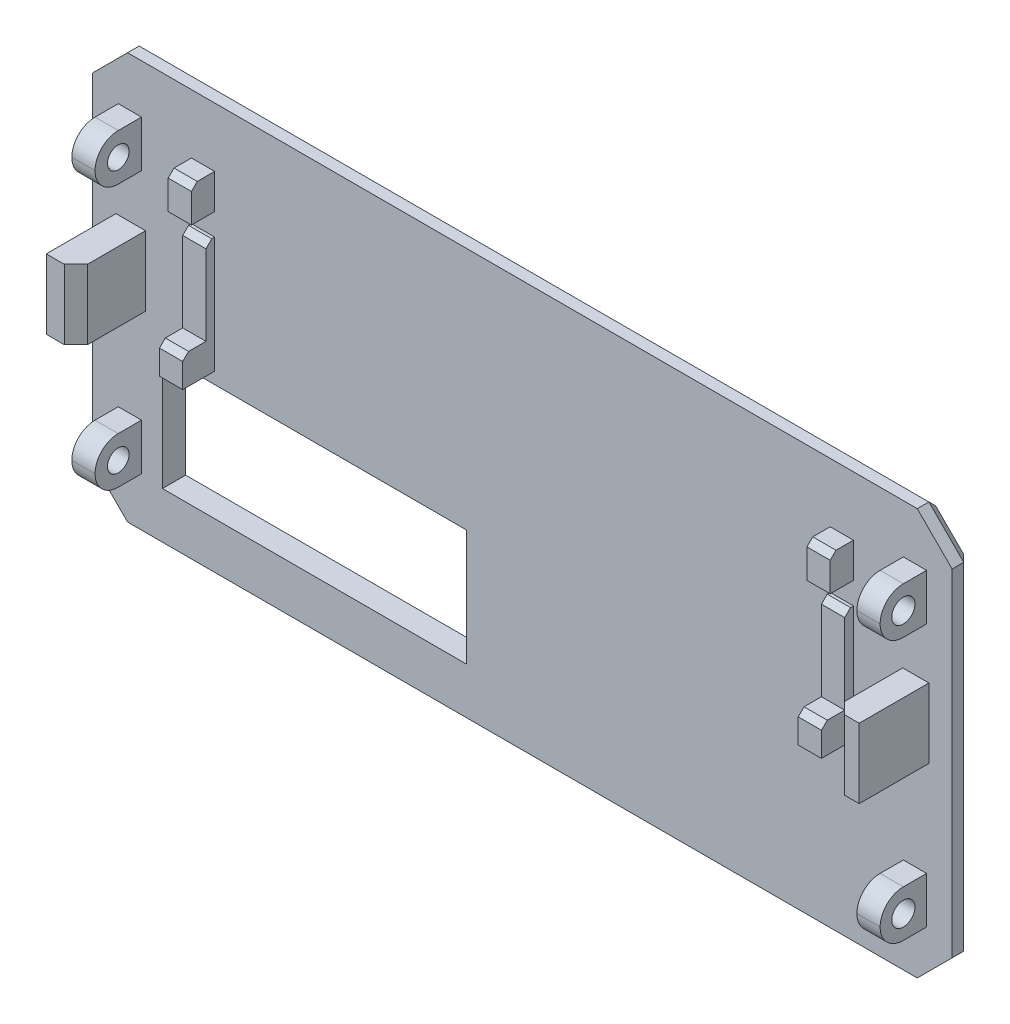
SolidWorks part; units mm, degrees
ref_plane "前视基准面" through (0, 0, 0) normal (0, 0, 1) x (1, 0, 0)
ref_plane "上视基准面" through (0, 0, 0) normal (0, 1, 0) x (1, 0, 0)
ref_plane "右视基准面" through (0, 0, 0) normal (1, 0, 0) x (0, 0, -1)
other "Configuration Table"
sketch "草图1" plane through (0, 0, 0) normal (0, 0, 1) x (1, 0, 0)
  line L0 (-39.7638, 14.7992) -> (-36.7638, 17.7992)
  line L5 (-36.7638, 17.7992) -> (31.2362, 17.7992)
  line L6 (-39.7638, 14.7992) -> (-39.7638, -14.2008)
  line L7 (-36.7638, -17.2008) -> (31.2362, -17.2008)
  line L8 (34.2362, 14.7992) -> (34.2362, -14.2008)
  line L9 (-39.7638, -14.2008) -> (-36.7638, -17.2008)
  line L10 (31.2362, -17.2008) -> (34.2362, -14.2008)
  line L11 (31.2362, 17.7992) -> (34.2362, 14.7992)
  point P0 (-39.7638, 17.7992)
  point P1 (34.2362, -17.2008)
  point P2 (-39.7638, -17.2008)
  point P3 (34.2362, 17.7992)
  dimension "D1" = 74
  dimension "D2" = 35
extrude "凸台-拉伸1" add sketch "草图1" along normal blind 2
chamfer "倒角1" distance 1 angle 45 8 edges at (-38.2638, 16.2992, 0) (-2.7638, -17.2008, 0) (-39.7638, 0.2992, 0) (-38.2638, -15.7008, 0) (32.7362, -15.7008, 0) (34.2362, 0.2992, 0) (32.7362, 16.2992, 0) (-2.7638, 17.7992, 0)
sketch "草图3" plane through (0, 0, 2) normal (0, 0, 1) x (1, 0, 0)
  line L0 (-36.7638, 17.7992) -> (31.2362, 17.7992) construction
  line L1 (-37.5638, 13.5992) -> (-35.5638, 13.5992)
  line L2 (-37.5638, 13.5992) -> (-37.5638, 9.5992)
  line L3 (-37.5638, 9.5992) -> (-35.5638, 9.5992)
  line L4 (-35.5638, 13.5992) -> (-35.5638, 9.5992)
  line L5 (-37.5638, -13.0008) -> (-35.5638, -13.0008)
  line L6 (-37.5638, -13.0008) -> (-37.5638, -9.0008)
  line L7 (-37.5638, -9.0008) -> (-35.5638, -9.0008)
  line L8 (-35.5638, -13.0008) -> (-35.5638, -9.0008)
  line L9 (32.0362, 13.5992) -> (30.0362, 13.5992)
  line L10 (32.0362, 13.5992) -> (32.0362, 9.5992)
  line L11 (32.0362, 9.5992) -> (30.0362, 9.5992)
  line L12 (30.0362, 13.5992) -> (30.0362, 9.5992)
  line L13 (32.0362, -13.0008) -> (30.0362, -13.0008)
  line L14 (32.0362, -13.0008) -> (32.0362, -9.0008)
  line L15 (32.0362, -9.0008) -> (30.0362, -9.0008)
  line L16 (30.0362, -13.0008) -> (30.0362, -9.0008)
  line L17 (-39.7638, -14.2008) -> (-39.7638, 14.7992) construction
  line L18 (34.2362, 14.7992) -> (34.2362, -14.2008) construction
  line L19 (31.2362, -17.2008) -> (-36.7638, -17.2008) construction
  point P20 (0, 0)
  point P21 (0, 0)
  point P22 (0, 0)
  point P23 (0, 0)
  point P24 (0, 0)
  point P35 (0, 0)
  point P36 (0, 0)
  point P37 (0, 0)
  point P38 (0, 0)
  dimension "D1" = 2
  dimension "D2" = 4
  dimension "D3" = 4.2
  dimension "D4" = 2.2
  dimension "D5" = 2.2
  dimension "D6" = 4.2
extrude "凸台-拉伸2" add sketch "草图3" along normal blind 4
fillet "圆角1" radius 2 8 edges at (31.0362, 13.5992, 6) (31.0362, 9.5992, 6) (31.0362, -9.0008, 6) (31.0362, -13.0008, 6) (-36.5638, -13.0008, 6) (-36.5638, -9.0008, 6) (-36.5638, 13.5992, 6) (-36.5638, 9.5992, 6)
sketch "草图4" plane through (32.0362, 0, 0) normal (1, 0, 0) x (0, 0, -1)
  circle A0 centre (-4, 11.5992) radius 1
  circle A1 centre (-4, -11.0008) radius 1
  dimension "D1" = 2
extrude "切除-拉伸1" cut sketch "草图4" against normal up to next (2 mm away) draft 2
sketch "草图5" plane through (-37.5638, 0, 0) normal (-1, 0, 0) x (0, 0, 1)
  circle A0 centre (4, 11.5992) radius 1
  circle A1 centre (4, -11.0008) radius 1
  dimension "D1" = 2
extrude "切除-拉伸2" cut sketch "草图5" against normal up to next (2 mm away) draft 2
sketch "草图6" plane through (0, 0, 2) normal (0, 0, 1) x (1, 0, 0)
  line L0 (31.2362, 17.7992) -> (-36.7638, 17.7992) construction
  line L1 (-31.2638, 7.7992) -> (-29.2638, 7.7992)
  line L2 (-31.2638, 7.7992) -> (-31.2638, -2.2008)
  line L3 (-31.2638, -2.2008) -> (-29.2638, -2.2008)
  line L4 (-29.2638, 7.7992) -> (-29.2638, -2.2008)
  line L5 (23.7362, 7.7992) -> (25.7362, 7.7992)
  line L6 (23.7362, 7.7992) -> (23.7362, -2.2008)
  line L7 (23.7362, -2.2008) -> (25.7362, -2.2008)
  line L8 (25.7362, 7.7992) -> (25.7362, -2.2008)
  line L9 (-39.7638, 14.7992) -> (-39.7638, -14.2008) construction
  line L10 (34.2362, -14.2008) -> (34.2362, 14.7992) construction
  dimension "D1" = 10
  dimension "D2" = 10
  dimension "D3" = 8.5
  dimension "D4" = 8.5
  dimension "D5" = 10
  dimension "D6" = 2
extrude "凸台-拉伸3" add sketch "草图6" along normal blind 0.75
sketch "草图7" plane through (0, 0, 2.75) normal (0, 0, 1) x (1, 0, 0)
  line L0 (-29.2638, -2.2008) -> (-29.2638, 7.7992) construction
  line L1 (-31.2638, -2.2008) -> (-29.2638, -2.2008)
  line L2 (-31.2638, -2.2008) -> (-31.2638, 0.3992)
  line L3 (-31.2638, 0.3992) -> (-29.2638, 0.3992)
  line L4 (-29.2638, -2.2008) -> (-29.2638, 0.3992)
  line L5 (25.7362, -2.2008) -> (25.7362, 7.7992) construction
  line L6 (23.7362, -2.2008) -> (25.7362, -2.2008)
  line L7 (23.7362, -2.2008) -> (23.7362, 0.3992)
  line L8 (23.7362, 0.3992) -> (25.7362, 0.3992)
  line L9 (25.7362, -2.2008) -> (25.7362, 0.3992)
  dimension "D1" = 2.6
extrude "凸台-拉伸4" add sketch "草图7" along normal blind 2
chamfer "倒角2" distance 0.5 angle 45 4 edges at (24.7362, 7.7992, 2.75) (24.7362, 0.3992, 4.75) (-30.2638, 7.7992, 2.75) (-30.2638, 0.3992, 4.75)
sketch "草图8" plane through (0, 0, 2) normal (0, 0, 1) x (1, 0, 0)
  line L0 (-37.7638, 13.9708) -> (-37.7638, -13.3724) construction
  line L1 (-37.7638, 5.2992) -> (-35.2138, 5.2992)
  line L2 (-37.7638, 5.2992) -> (-37.7638, -0.7008)
  line L3 (-37.7638, -0.7008) -> (-35.2138, -0.7008)
  line L4 (-35.2138, 5.2992) -> (-35.2138, -0.7008)
  line L5 (31.2362, 17.7992) -> (-36.7638, 17.7992) construction
  line L6 (32.2362, -13.3724) -> (32.2362, 13.9708) construction
  line L7 (32.2362, 5.2992) -> (29.9862, 5.2992)
  line L8 (32.2362, 5.2992) -> (32.2362, -0.7008)
  line L9 (32.2362, -0.7008) -> (29.9862, -0.7008)
  line L10 (29.9862, 5.2992) -> (29.9862, -0.7008)
  dimension "D1" = 12.5
  dimension "D2" = 6
  dimension "D3" = 2.55
  dimension "D4" = 2.25
extrude "凸台-拉伸5" add sketch "草图8" along normal blind 6
chamfer "倒角3" distance 1 angle 45 2 edges at (29.9862, 2.2992, 8) (-35.2138, 2.2992, 8)
sketch "草图9" plane through (0, 0, 2) normal (0, 0, 1) x (1, 0, 0)
  line L0 (31.2362, 17.7992) -> (-36.7638, 17.7992) construction
  line L1 (-31.2638, 12.6992) -> (-29.2638, 12.6992)
  line L2 (-31.2638, 12.6992) -> (-31.2638, 9.6992)
  line L3 (-31.2638, 9.6992) -> (-29.2638, 9.6992)
  line L4 (-29.2638, 12.6992) -> (-29.2638, 9.6992)
  line L5 (23.7362, 12.6992) -> (25.7362, 12.6992)
  line L6 (23.7362, 12.6992) -> (23.7362, 9.6992)
  line L7 (23.7362, 9.6992) -> (25.7362, 9.6992)
  line L8 (25.7362, 12.6992) -> (25.7362, 9.6992)
  line L9 (34.2362, -14.2008) -> (34.2362, 14.7992) construction
  line L10 (-39.7638, 14.7992) -> (-39.7638, -14.2008) construction
  dimension "D1" = 5.1
  dimension "D2" = 8.5
  dimension "D3" = 2
  dimension "D4" = 3
  dimension "D5" = 8.5
extrude "凸台-拉伸6" add sketch "草图9" along normal blind 2
chamfer "倒角4" distance 0.5 angle 45 2 edges at (24.7362, 12.6992, 4) (-30.2638, 12.6992, 4)
sketch "草图10" plane through (0, 0, 0) normal (0, 0, -1) x (-1, 0, 0)
  line L0 (36.7638, -17.2008) -> (-31.2362, -17.2008) construction
  line L1 (7.5638, -3.2008) -> (33.7638, -3.2008)
  line L2 (7.5638, -3.2008) -> (7.5638, -13.2008)
  line L3 (7.5638, -13.2008) -> (33.7638, -13.2008)
  line L4 (33.7638, -3.2008) -> (33.7638, -13.2008)
  line L5 (39.7638, 14.7992) -> (39.7638, -14.2008) construction
  dimension "D1" = 4
  dimension "D2" = 10
  dimension "D3" = 6
  dimension "D4" = 26.2
extrude "切除-拉伸3" cut sketch "草图10" against normal up to next
